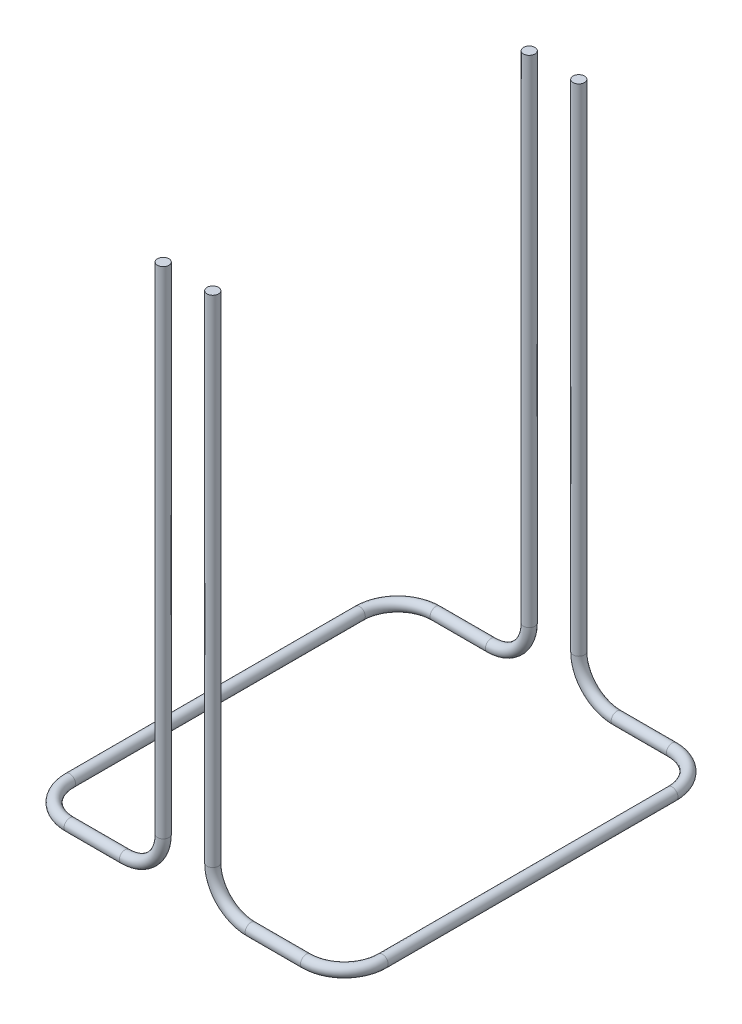
SolidWorks part; units mm, degrees
ref_plane "前视基准面" through (0, 0, 0) normal (0, 0, 1) x (1, 0, 0)
ref_plane "上视基准面" through (0, 0, 0) normal (0, 1, 0) x (1, 0, 0)
ref_plane "右视基准面" through (0, 0, 0) normal (1, 0, 0) x (0, 0, -1)
sketch3d "3D草图1"
  line L0 (0, 0, 0) -> (0, 51.939, 0) construction
  line L1 (32.4951, 700.5634, 0) -> (32.4951, 50.5634, 0)
  line L2 (82.4951, 0.5634, 0) -> (154.9992, 0.5634, 0)
  line L3 (204.9992, 0.5634, -50) -> (204.9992, 0.5634, -430)
  line L4 (154.9992, 0.5634, -480) -> (82.4951, 0.5634, -480)
  line L5 (32.4951, 50.5634, -480) -> (32.4951, 700.5634, -480)
  line L6 (-32.4951, 50.5634, -480) -> (-32.4951, 700.5634, -480)
  line L7 (-154.9992, 0.5634, -480) -> (-82.4951, 0.5634, -480)
  line L8 (-204.9992, 0.5634, -50) -> (-204.9992, 0.5634, -430)
  line L9 (-82.4951, 0.5634, 0) -> (-154.9992, 0.5634, 0)
  line L10 (-32.4951, 700.5634, 0) -> (-32.4951, 50.5634, 0)
  arc A0 (82.4951, 0.5634, -480) -> (32.4951, 50.5634, -480) centre (82.4951, 50.5634, -480) ccw
  arc A1 (204.9992, 0.5634, -430) -> (154.9992, 0.5634, -480) centre (154.9992, 0.5634, -430) ccw
  arc A2 (154.9992, 0.5634, 0) -> (204.9992, 0.5634, -50) centre (154.9992, 0.5634, -50) ccw
  arc A3 (32.4951, 50.5634, 0) -> (82.4951, 0.5634, 0) centre (82.4951, 50.5634, 0) ccw
  arc A4 (-82.4951, 0.5634, 0) -> (-32.4951, 50.5634, 0) centre (-82.4951, 50.5634, 0) cw
  arc A5 (-204.9992, 0.5634, -50) -> (-154.9992, 0.5634, 0) centre (-154.9992, 0.5634, -50) cw
  arc A6 (-154.9992, 0.5634, -480) -> (-204.9992, 0.5634, -430) centre (-154.9992, 0.5634, -430) cw
  arc A7 (-32.4951, 50.5634, -480) -> (-82.4951, 0.5634, -480) centre (-82.4951, 50.5634, -480) cw
  point P11 (32.4951, 0.5634, -480)
  point P12 (82.4951, 50.5634, -530)
  point P15 (204.9992, 0.5634, -480)
  point P16 (154.9992, 50.5634, -430)
  point P19 (204.9992, 0.5634, 0)
  point P20 (154.9992, 50.5634, -50)
  point P23 (32.4951, 0.5634, 0)
  point P24 (82.4951, 50.5634, 50)
  point P28 (-82.4951, 50.5634, 50)
  point P32 (-154.9992, 50.5634, -50)
  point P36 (-154.9992, 50.5634, -430)
  point P40 (-82.4951, 50.5634, -530)
  point P43 (-32.4951, 0.5634, 0)
  point P44 (-204.9992, 0.5634, 0)
  point P45 (-204.9992, 0.5634, -480)
  point P46 (-32.4951, 0.5634, -480)
  point P47 (0, 0, 0)
  dimension "D5" = 50
  dimension "D1" = 700
  dimension "D2" = 205
  dimension "D3" = 32.4951
  dimension "D4" = 480
sweep "扫描1" add path "3D草图1" circular profile diameter 15 parameters "D3"=15
sweep "扫描2" add path "3D草图1<4>" circular profile diameter 15 parameters "D3"=15
sketch3d "3D草图1<4>" same geometry as "3D草图1"
